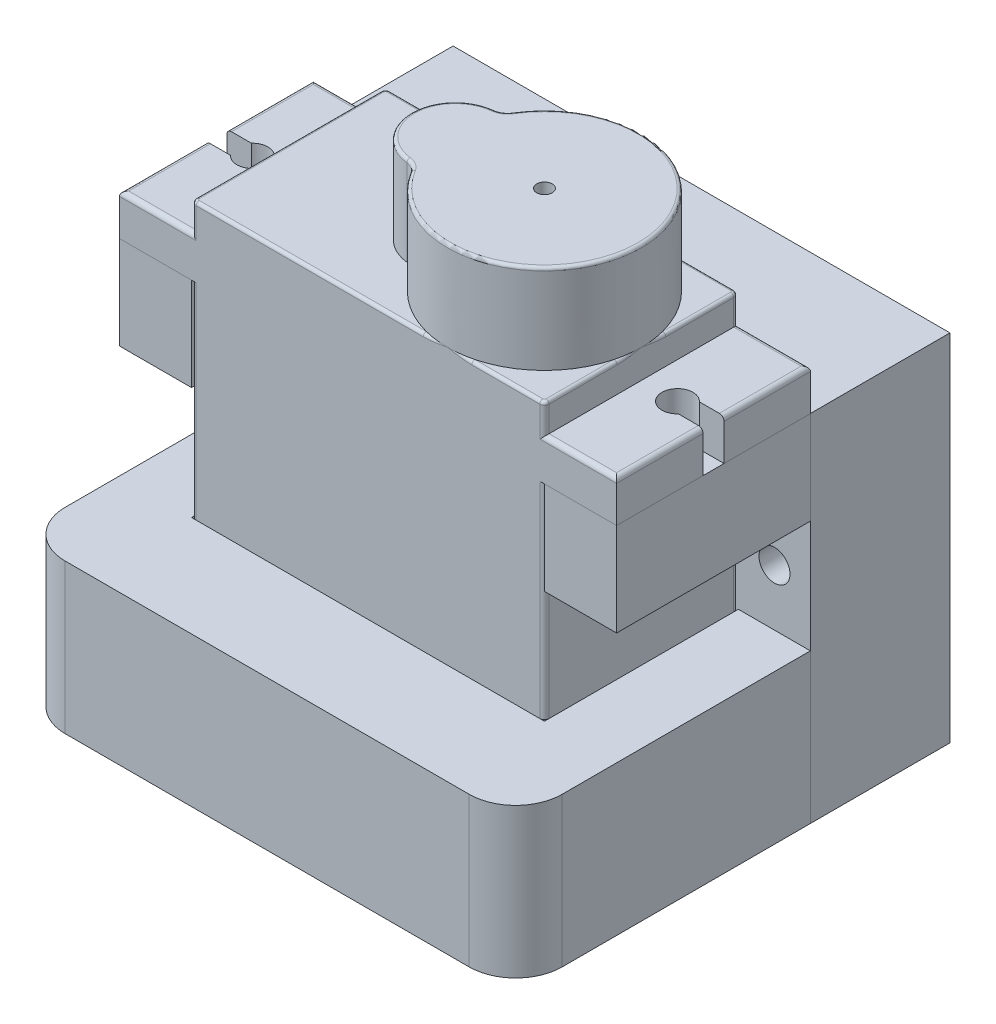
SolidWorks part; units mm, degrees
material "ABS"
ref_plane "Front Plane" through (0, 0, 0) normal (0, 0, 1) x (1, 0, 0)
ref_plane "Top Plane" through (0, 0, 0) normal (0, 1, 0) x (1, 0, 0)
ref_plane "Right Plane" through (0, 0, 0) normal (1, 0, 0) x (0, 0, -1)
sketch "Sketch1" plane through (0, 0, 0) normal (0, 1, 0) x (1, 0, 0)
  line L1 (0, 0) -> (22.75, 0)
  line L2 (0, 0) -> (0, 12.5)
  line L3 (0, 12.5) -> (22.75, 12.5)
  line L4 (22.75, 0) -> (22.75, 12.5)
  dimension "D1" = 12.5
  dimension "D2" = 22.75
extrude "Boss-Extrude1" add sketch "Sketch1" along normal blind 22.75 contours L3 L4 L1 L2
ref_plane "Plane1" through (0, 18.25, 0) normal (0, -1, 0) x (-1, 0, 0)
sketch "Sketch2" plane through (0, 18.25, 0) normal (0, -1, 0) x (-1, 0, 0)
  line L0 (0, 12.5) -> (-22.75, 12.5) construction
  line L1 (-27.4, 0) -> (4.65, 0)
  line L2 (-27.4, 0) -> (-27.4, 12.5)
  line L3 (-27.4, 12.5) -> (4.65, 12.5)
  line L4 (4.65, 0) -> (4.65, 12.5)
  line L5 (0, 0) -> (-22.75, 0) construction
  line L6 (-22.75, 0) -> (-22.75, 12.5) construction
  line L7 (0, 0) -> (0, 12.5) construction
  dimension "D1" = 4.65
  dimension "D2" = 4.65
extrude "Boss-Extrude2" add sketch "Sketch2" against normal blind 2.65
sketch "Sketch3" plane through (0, 0, 0) normal (0, -1, 0) x (1, 0, 0)
  line L0 (22.6, -12.35) -> (22.6, -0.15)
  line L1 (22.75, -12.5) -> (0, -12.5)
  line L2 (22.75, -12.5) -> (22.75, 0)
  line L3 (22.75, 0) -> (0, 0)
  line L4 (0, -12.5) -> (0, 0)
  line L5 (22.6, -0.15) -> (0.15, -0.15)
  line L6 (0.15, -12.35) -> (0.15, -0.15)
  line L7 (22.6, -12.35) -> (0.15, -12.35)
  dimension "D1" = 0.15
extrude "Cut-Extrude1" cut sketch "Sketch3" against normal blind 5
sketch "Sketch4" plane through (22.6, 0, 0) normal (1, 0, 0) x (0, 0, -1)
  line L0 (6.25, -1.4795) -> (6.25, 16.7983) construction
  line L1 (12.5, 5) -> (0, 5) construction
  line L2 (4.325, 5) -> (8.175, 5)
  line L3 (4.325, 5) -> (4.325, 3.77)
  line L4 (4.325, 3.77) -> (8.175, 3.77)
  line L5 (8.175, 5) -> (8.175, 3.77)
  line L6 (12.35, 0) -> (0.15, 0) construction
  point P8 (6.25, 0)
  dimension "D1" = 3.85
  dimension "D2" = 1.23
extrude "Cut-Extrude2" cut sketch "Sketch4" against normal blind 2
sketch "Sketch5" plane through (0, 22.75, 0) normal (0, 1, 0) x (1, 0, 0)
  line L0 (22.75, 0) -> (22.75, 12.5) construction
  line L1 (0, 12.5) -> (22.75, 12.5) construction
  line L2 (0, 0) -> (22.75, 0) construction
  circle A0 centre (16.5, 6.25) radius 6.25
extrude "Boss-Extrude3" add sketch "Sketch5" along normal blind 5.75
sketch "Sketch6" plane through (0, 22.75, 0) normal (0, 1, 0) x (1, 0, 0)
  line L0 (0, 0) -> (0, 12.5) construction
  line L1 (-9.0126, 6.25) -> (31.0272, 6.25) construction
  circle A0 centre (10.75, 6.25) radius 2.825
  point P0 (0, 6.25)
  point P7 (16.5, 6.25)
  dimension "D1" = 5.65
  dimension "D2" = 5.75
extrude "Boss-Extrude4" add sketch "Sketch6" along normal blind 5.75
fillet "Fillet0.3mm" radius 0.3 18 edges at (22.6, 2.5, -0.15) (0.15, 2.5, -0.15) (0.15, 2.5, -12.35) (22.6, 2.5, -12.35) (27.4, 20.9, -6.25) (25.075, 20.9, -12.5) (-2.325, 20.9, -12.5) (-4.65, 20.9, -6.25) (25.075, 20.9, 0) (-2.325, 20.9, 0) (0, 11.625, 0) (0, 21.825, 0) (0, 21.825, -12.5) (0, 11.625, -12.5) (22.75, 21.825, 0) (22.75, 21.825, -12.5) (22.75, 11.625, 0) (22.75, 11.625, -12.5)
fillet "Fillet1.0mm" radius 1 2 edges at (10.9222, 25.625, -3.4303) (10.9222, 25.625, -9.0697)
fillet "Fillet0.2mm" radius 0.2 15 edges at (10.8619, 28.5, -3.2932) (7.925, 28.5, -6.25) (10.8619, 28.5, -9.2068) (0.0879, 22.75, -0.0879) (0, 22.75, -6.25) (0.0879, 22.75, -12.4121) (8.4, 22.75, -12.5) (19.475, 22.75, -12.5) (22.6621, 22.75, -12.4121) (22.75, 22.75, -9.225) (22.75, 22.75, -3.275) (22.6621, 22.75, -0.0879) (19.475, 22.75, 0) (22.75, 28.5, -6.25) (8.4, 22.75, 0)
sketch "Sketch7" plane through (0, 28.5, 0) normal (0, 1, 0) x (1, 0, 0)
  circle A0 centre (16.5, 6.25) radius 0.5
  dimension "D1" = 1
extrude "Cut-Extrude3" cut sketch "Sketch7" against normal blind 2
sketch "Sketch8" plane through (0, 20.9, 0) normal (0, 1, 0) x (1, 0, 0)
  line L0 (27.4, 12.5) -> (27.4, 0) construction
  line L1 (14.9316, 0) -> (0.3, 0) construction
  line L2 (11.375, -5.8389) -> (11.375, 15.897) construction
  line L3 (33.0701, 6.25) -> (-8.9718, 6.25) construction
  line L4 (22.75, 0.3) -> (22.75, 12.2) construction
  circle A0 centre (25.075, 6.25) radius 1
  circle A1 centre (-2.325, 6.25) radius 1
  point P0 (27.4, 6.25)
  point P1 (11.375, 0)
  dimension "D2" = 2
  dimension "D1" = 16.025
  dimension "D3" = 2.325
extrude "Cut-Extrude4" cut sketch "Sketch8" against normal through all
sketch "Sketch9" plane through (0, 20.9, 0) normal (0, 1, 0) x (1, 0, 0)
  line L0 (27.1, 0.3) -> (27.1, 12.2) construction
  line L1 (31.0681, 6.25) -> (-10.4426, 6.25) construction
  line L2 (-4.65, 0) -> (-4.65, 12.5) construction
  line L3 (27.4, 5.575) -> (24.9, 5.575)
  line L4 (27.4, 5.575) -> (27.4, 6.925)
  line L5 (27.4, 6.925) -> (24.9, 6.925)
  line L6 (24.9, 5.575) -> (24.9, 6.925)
  line L7 (27.4, 5.575) -> (24.9, 6.925) construction
  line L8 (27.4, 6.925) -> (24.9, 5.575) construction
  line L9 (-2.15, 5.575) -> (-4.65, 5.575)
  line L10 (-2.15, 5.575) -> (-2.15, 6.925)
  line L11 (-2.15, 6.925) -> (-4.65, 6.925)
  line L12 (-4.65, 5.575) -> (-4.65, 6.925)
  line L13 (-2.15, 5.575) -> (-4.65, 6.925) construction
  line L14 (-2.15, 6.925) -> (-4.65, 5.575) construction
  line L15 (27.4, 12.5) -> (27.4, 0) construction
  point P0 (27.1, 6.25)
  point P5 (26.15, 6.25)
  point P10 (-3.4, 6.25)
  dimension "D1" = 1.35
  dimension "D2" = 1.35
  dimension "D3" = 2.5
  dimension "D4" = 2.5
extrude "Cut-Extrude5" cut sketch "Sketch9" against normal through all
sketch "Croquis1" plane through (0, 0, -12.5) normal (0, 0, -1) x (-1, 0, 0)
  line L1 (-22.45, 18.25) -> (-27.4, 18.25) construction
  line L2 (4.65, 18.25) -> (-0.3, 18.25) construction
  line L6 (-22.75, 18.25) -> (-27.39, 18.25) construction
  line L7 (4.64, 18.25) -> (0, 18.25) construction
  line L23 (-27.39, 2.8255) -> (-27.39, 18.25) construction
  line L25 (-27.39, 2.8255) -> (4.64, 2.8255) construction
  line L27 (-22.75, 18.25) -> (0, 18.25) construction
  line L28 (-27.39, 18.25) -> (4.64, 18.25)
  line L29 (-22.75, 18.25) -> (0, 18.25) construction
  line L30 (4.64, 2.8255) -> (4.64, 18.25) construction
  line L31 (-27.39, 18.25) -> (-27.39, -4.64)
  line L32 (-27.39, -4.64) -> (4.64, -4.64)
  line L33 (4.64, 18.25) -> (4.64, -4.64)
  point P10 (4.64, 22.89)
  point P14 (4.64, 5)
  point P19 (-27.39, 12.4655)
  point P20 (-27.39, 22.89)
  dimension "D1" = 32.03
  dimension "D2" = 22.89
extrude "Saliente-Extruir6" add sketch "Croquis1" along normal blind 9 separate body
sketch "Croquis2" plane through (0, 0, -12.5) normal (0, 0, 1) x (1, 0, 0)
  line L0 (-4.65, 20.6) -> (-4.65, 18.25) construction
  line L1 (-4.65, 18.25) -> (0, 18.25)
  line L2 (-4.65, 18.25) -> (-4.65, 12.25)
  line L3 (-4.65, 12.25) -> (0, 12.25)
  line L4 (0, 18.25) -> (0, 12.25)
  line L5 (0.3, 18.25) -> (-4.65, 18.25) construction
  line L6 (0, 5) -> (0, 18.25) construction
  line L7 (11.375, -4.64) -> (11.375, 34.1439) construction
  line L8 (27.39, -4.64) -> (-4.64, -4.64) construction
  line L9 (27.4, 12.25) -> (22.75, 12.25)
  line L10 (22.75, 18.25) -> (22.75, 12.25)
  line L11 (27.4, 18.25) -> (22.75, 18.25)
  line L12 (27.4, 18.25) -> (27.4, 12.25)
  dimension "D1" = 6
extrude "Saliente-Extruir7" add sketch "Croquis2" along normal up to vertex (12.5 mm away) up to point (-4.65, 18.25, 0)
sketch "Croquis3" plane through (0, 0, 0) normal (0, 1, 0) x (1, 0, 0)
  line L0 (0, 12.5) -> (-4.64, 12.5)
  line L1 (-4.64, 12.5) -> (0, 12.5) construction
  line L2 (-4.64, 12.5) -> (-4.64, -3.5035)
  line L3 (-1.64, -6.5035) -> (24.3984, -6.5035)
  line L4 (27.3984, -3.5019) -> (27.39, 12.5)
  line L5 (27.39, 12.5) -> (22.75, 12.5)
  line L6 (22.75, 12.5) -> (22.75, 0)
  line L7 (22.75, 0) -> (0, 0)
  line L8 (0, 0) -> (0, 12.5)
  arc A0 (24.3984, -6.5035) -> (27.3984, -3.5019) centre (24.3984, -3.5035) ccw
  arc A1 (-4.64, -3.5035) -> (-1.64, -6.5035) centre (-1.64, -3.5035) ccw
  dimension "D1" = 3
extrude "Saliente-Extruir8" add sketch "Croquis3" along normal up to vertex (5 mm away) and the other way up to vertex (4.64 mm away) up to point (22.45, 5, 0) other way up to point (27.39, -4.64, -12.5)
sketch "Croquis4" plane through (0, -4.64, 0) normal (0, -1, 0) x (1, 0, 0)
  line L1 (22.75, 0) -> (0, 0)
  line L2 (22.75, 0) -> (22.75, -12.5)
  line L3 (22.75, -12.5) -> (0, -12.5)
  line L4 (0, 0) -> (0, -12.5)
extrude "Saliente-Extruir9" add sketch "Croquis4" against normal up to surface (4.64 mm away) up to face at (11.375, 0, -6.25)
sketch "Croquis5" plane through (0, 0, 0) normal (0, 1, 0) x (1, 0, 0)
  line L0 (11.3792, -6.5035) -> (11.3792, 14.9027) construction
  line L1 (-1.64, -6.5035) -> (24.3984, -6.5035) construction
  circle A0 centre (-2.325, 6.25) radius 1
  arc A1 (-3.0628, 5.575) -> (-3.0628, 6.925) centre (-2.325, 6.25) ccw construction
  circle A2 centre (25.0834, 6.25) radius 1
extrude "Cortar-Extruir1" cut sketch "Croquis5" along direction (0, 1, 0) on the side against the normal up to surface (-12.25 mm away) from surface up to face at (-2.788, 12.25, -7.5) starting at face at (11.375, 18.25, -9.8333)
sketch "Croquis6" plane through (0, 0, 0) normal (0, 0, 1) x (1, 0, 0)
  line L0 (-4.64, 5) -> (0, 12.25) construction
  line L1 (0, 12.25) -> (-4.65, 12.25) construction
  line L2 (-4.65, 12.25) -> (0, 5) construction
  line L4 (11.3792, -4.64) -> (11.3792, 19.599) construction
  line L5 (-1.64, -4.64) -> (24.3984, -4.64) construction
  circle A0 centre (-2.32, 8.625) radius 1
  circle A1 centre (25.0784, 8.625) radius 1
  dimension "D1" = 2
extrude "Cortar-Extruir2" cut sketch "Croquis6" along direction (0, 0, -1) on the side against the normal up to surface (21.5 mm away) up to face at (11.375, 6.805, -21.5)
sketch "Croquis7" plane through (0, 28.5, 0) normal (0, 1, 0) x (1, 0, 0)
  circle A0 centre (16.5, 6.25) radius 3.8
  dimension "D1" = 7.6
extrude "Cortar-Extruir3" cut sketch "Croquis7" against normal blind 43
